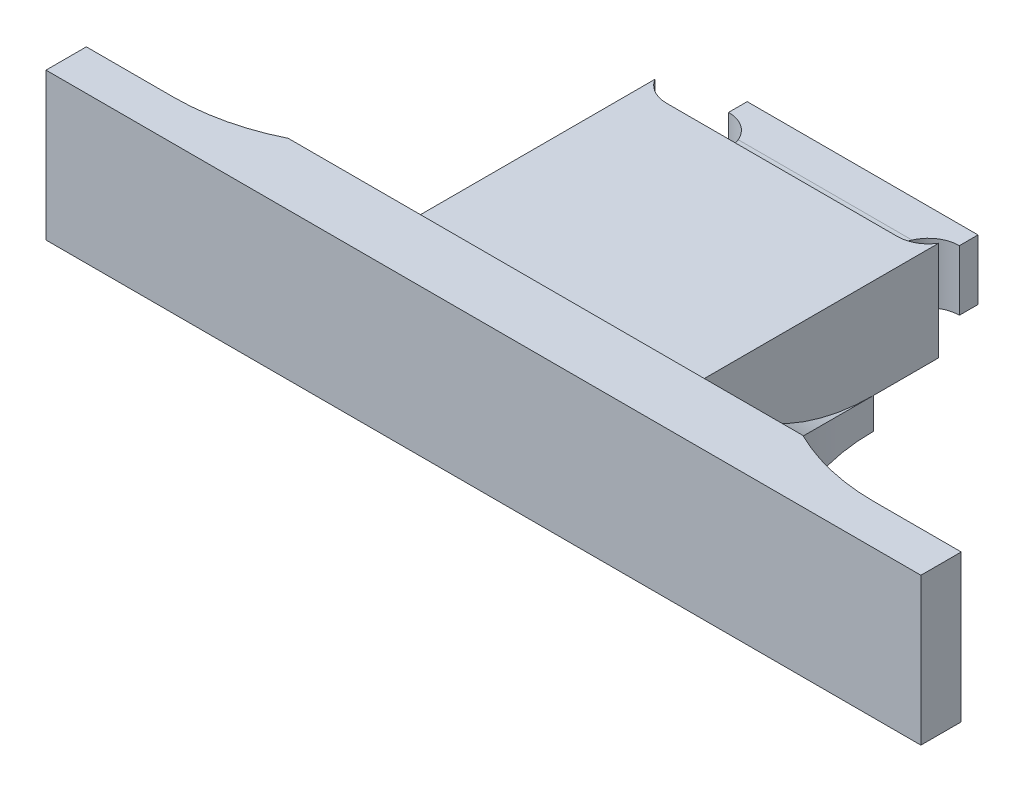
SolidWorks part; units mm, degrees
ref_plane "Front Plane" through (0, 0, 0) normal (0, 0, 1) x (1, 0, 0)
ref_plane "Top Plane" through (0, 0, 0) normal (0, 1, 0) x (1, 0, 0)
ref_plane "Right Plane" through (0, 0, 0) normal (1, 0, 0) x (0, 0, -1)
sketch "Sketch2" plane through (0, 0, 138.6086) normal (0, 0, 1) x (1, 0, 0)
  line L0 (70.4445, 0) -> (70.4445, 5) construction
  line L1 (-70.5526, 0) -> (70.4445, 0)
  line L2 (-70.5526, 0) -> (-70.5526, 23.7194)
  line L3 (-70.5526, 23.7194) -> (70.4445, 23.7194)
  line L4 (70.4445, 0) -> (70.4445, 23.7194)
extrude "Boss-Extrude1" add sketch "Sketch2" along normal blind 40
sketch "Sketch3" plane through (-70.5526, 0, 0) normal (-1, 0, 0) x (0, 0, 1)
  line L0 (138.6086, 23.7194) -> (138.6086, 0) construction
  line L3 (138.6086, 5) -> (152.3731, 5)
  line L4 (178.6086, 23.7194) -> (138.6086, 23.7194) construction
  line L5 (158.6086, 23.7194) -> (178.6086, 23.7194)
  line L8 (138.6086, 23.7194) -> (138.6086, 0)
  line L9 (138.6086, 0) -> (178.6086, 0)
  line L10 (178.6086, 0) -> (178.6086, 23.7194)
  line L11 (178.6086, 23.7194) -> (138.6086, 23.7194)
  line L12 (138.6086, 23.7194) -> (138.6086, 0)
  line L13 (138.6086, 0) -> (178.6086, 0)
  line L14 (178.6086, 0) -> (178.6086, 23.7194)
  line L15 (178.6086, 23.7194) -> (138.6086, 23.7194)
  arc A0 (138.6086, 5) -> (168.6086, 23.7194) centre (138.6086, 38.399) ccw
  point P2 (158.6086, 23.7194)
  point P6 (0, 0)
  point P7 (0, 0)
  point P8 (0, 0)
  point P9 (0, 0)
  point P10 (0, 0)
  point P11 (0, 0)
  point P21 (168.6086, 23.7194)
  line M6 (138.6086, 23.7194) -> (138.6086, 0)
  line M9 (178.6086, 23.7194) -> (138.6086, 23.7194)
  dimension "D2" = 5
  dimension "D3" = 23.7194
  dimension "D1" = 0
extrude "Cut-Extrude1" cut sketch "Sketch3" against normal through all contours M6 M9 region at (-70.5526, 16.0164, 150.4428)
sketch "Sketch4" plane through (0, 5, 0) normal (0, 1, 0) x (1, 0, 0)
  line L0 (-0.0541, -138.6086) -> (-0.0541, -183.6086)
  line L1 (70.4445, -138.6086) -> (-70.5526, -138.6086) construction
  line L2 (70.4445, -168.6086) -> (-70.5526, -168.6086) construction
  line L4 (-22.9249, -168.6086) -> (-22.9249, -128.1086)
  line L9 (-0.6345, -168.6086) -> (0.8576, -168.6086) construction
  line L10 (22.8168, -168.6086) -> (-22.9249, -168.6086)
  line L11 (22.8168, -168.6086) -> (22.8168, -128.1086)
  line L15 (-18.6541, -120.5086) -> (-18.6541, -117.5086)
  line L16 (-0.0541, -138.6086) -> (-0.0541, -118.0787) construction
  line L17 (-18.6541, -117.5086) -> (18.5459, -117.5086)
  line L19 (18.5459, -120.5086) -> (18.5459, -117.5086)
  circle A5 centre (18.5459, -125.5086) radius 5 construction
  arc A7 (18.5459, -120.5086) -> (22.8168, -128.1086) centre (18.5459, -125.5086) ccw
  circle A9 centre (-18.6541, -125.5086) radius 5
  arc A10 (-22.9249, -128.1086) -> (-18.6541, -120.5086) centre (-18.6541, -125.5086) ccw
  circle A11 centre (18.5459, -125.5086) radius 5
  arc A12 (18.5459, -120.5086) -> (22.8168, -128.1086) centre (18.5459, -125.5086) ccw
  point P31 (-0.0541, -117.5086)
  line M11 (-13.4387, -138.6086) -> (13.3306, -138.6086)
  arc M12 (13.3306, -138.6086) -> (8.0264, -116.1199) centre (18.5459, -125.5086) cw
  dimension "D3" = 3
  dimension "D1" = 0
  dimension "D4" = 0
extrude "Boss-Extrude2" add sketch "Sketch4" along normal blind 16 contours L17 M11 M12 | A7 L19 L17 L0 L10 L11 M12 M11 | A10 L4 L10 L0 L17 L15 M11 region at (11.7773, 5, 146.7916) region at (-9.2774, 5, 142.9696)
sketch "Sketch6" plane through (0, 23.7194, 0) normal (0, 1, 0) x (1, 0, 0)
  line L0 (-18.6541, -130.5086) -> (18.5459, -130.5086)
  line L1 (18.5459, -120.5086) -> (18.5459, -117.5086) construction
  line L2 (-18.6541, -117.5086) -> (18.5459, -117.5086) construction
  line L3 (-18.6541, -120.5086) -> (-18.6541, -117.5086) construction
  line L4 (18.5459, -117.5086) -> (18.5459, -120.5086)
  line L5 (-18.6541, -117.5086) -> (-18.6541, -120.5086)
  line L6 (18.5459, -117.5086) -> (-18.6541, -117.5086)
  arc A2 (18.5459, -120.5086) -> (22.8168, -128.1086) centre (18.5459, -125.5086) ccw construction
  arc A3 (-22.9249, -128.1086) -> (-18.6541, -120.5086) centre (-18.6541, -125.5086) ccw
  arc A4 (18.5459, -120.5086) -> (22.8168, -128.1086) centre (18.5459, -125.5086) ccw
  arc A5 (-22.9249, -128.1086) -> (-18.6541, -120.5086) centre (-18.6541, -125.5086) ccw construction
extrude "Cut-Extrude2" cut sketch "Sketch6" against normal blind 9 contours L0 region at (-0.0541, 23.7194, 123.7178)
fillet "Fillet1" radius 7 1 edges at (-0.0541, 14.7194, 130.5086)
sketch "Sketch10" plane through (0, 21, 0) normal (0, 1, 0) x (1, 0, 0)
  line L1 (-22.9249, -138.6086) -> (-22.9249, -167.1177) construction
  line L2 (-70.5526, -172.1086) -> (70.4445, -172.1086)
  line L3 (70.4445, -178.6086) -> (70.4445, -168.6086) construction
  line L4 (-70.5526, -168.6086) -> (-70.5526, -178.6086) construction
  line L5 (-0.0541, -167.1177) -> (-0.0541, -140.3068) construction
  line L6 (22.8168, -167.1177) -> (-22.9249, -167.1177) construction
  line L7 (70.4445, -168.6086) -> (70.4445, -178.6086)
  line L8 (70.4445, -178.6086) -> (-70.5526, -178.6086)
  line L9 (70.4445, -178.6086) -> (-70.5526, -178.6086) construction
  line L10 (-70.5526, -168.6086) -> (-70.5526, -178.6086)
  line L12 (-70.5526, -178.6086) -> (70.4445, -178.6086) construction
  line L13 (-22.9249, -138.6086) -> (-70.5526, -138.6086) construction
  line L16 (-70.5526, -138.6086) -> (-70.5526, -168.6086) construction
  line L17 (70.4445, -168.6086) -> (70.4445, -138.6086) construction
  line L18 (70.4445, -138.6086) -> (22.8168, -138.6086) construction
  line L19 (22.8168, -167.1177) -> (22.8168, -138.6086) construction
  line L20 (18.5459, -130.5086) -> (-18.6541, -130.5086) construction
  line L21 (-22.9249, -128.1086) -> (-22.9249, -167.1177) construction
  line L22 (22.8168, -167.1177) -> (22.8168, -128.1086) construction
  line L23 (70.4445, -178.6086) -> (70.4445, -168.6086)
  line L24 (-70.5526, -168.6086) -> (-70.5526, -178.6086)
  line L25 (-70.5526, -178.6086) -> (70.4445, -178.6086)
  line L26 (-22.9249, -138.6086) -> (-22.9249, -167.1177)
  line L27 (-22.9249, -138.6086) -> (-70.5526, -138.6086)
  line L28 (-70.5526, -138.6086) -> (-70.5526, -168.6086)
  line L29 (70.4445, -168.6086) -> (70.4445, -138.6086)
  line L30 (70.4445, -138.6086) -> (22.8168, -138.6086)
  line L31 (22.8168, -167.1177) -> (22.8168, -138.6086)
  line L32 (18.5459, -130.5086) -> (-18.6541, -130.5086)
  line L33 (-22.9249, -128.1086) -> (-22.9249, -167.1177)
  line L34 (22.8168, -167.1177) -> (22.8168, -128.1086)
  arc A0 (-22.9249, -138.6086) -> (-56.4249, -172.1086) centre (-56.4249, -138.6086) cw
  arc A2 (-22.9249, -128.1086) -> (-18.6541, -130.5086) centre (-18.6541, -125.5086) ccw construction
  arc A3 (18.5459, -130.5086) -> (22.8168, -128.1086) centre (18.5459, -125.5086) ccw construction
  arc A4 (-22.9249, -128.1086) -> (-18.6541, -130.5086) centre (-18.6541, -125.5086) ccw
  arc A5 (18.5459, -130.5086) -> (22.8168, -128.1086) centre (18.5459, -125.5086) ccw
  arc A6 (22.8168, -138.6086) -> (56.3168, -172.1086) centre (56.3168, -138.6086) ccw
  point P19 (-0.0541, -178.6086)
  dimension "D1" = 6.5
extrude "Cut-Extrude3" cut sketch "Sketch10" against normal through all both and the other way through all contours A0 L27 L28 L10 L2 | L30 A6 L2 L7 L29 region at (-49.6421, 21, 153.7111) region at (49.5339, 21, 153.7111)
